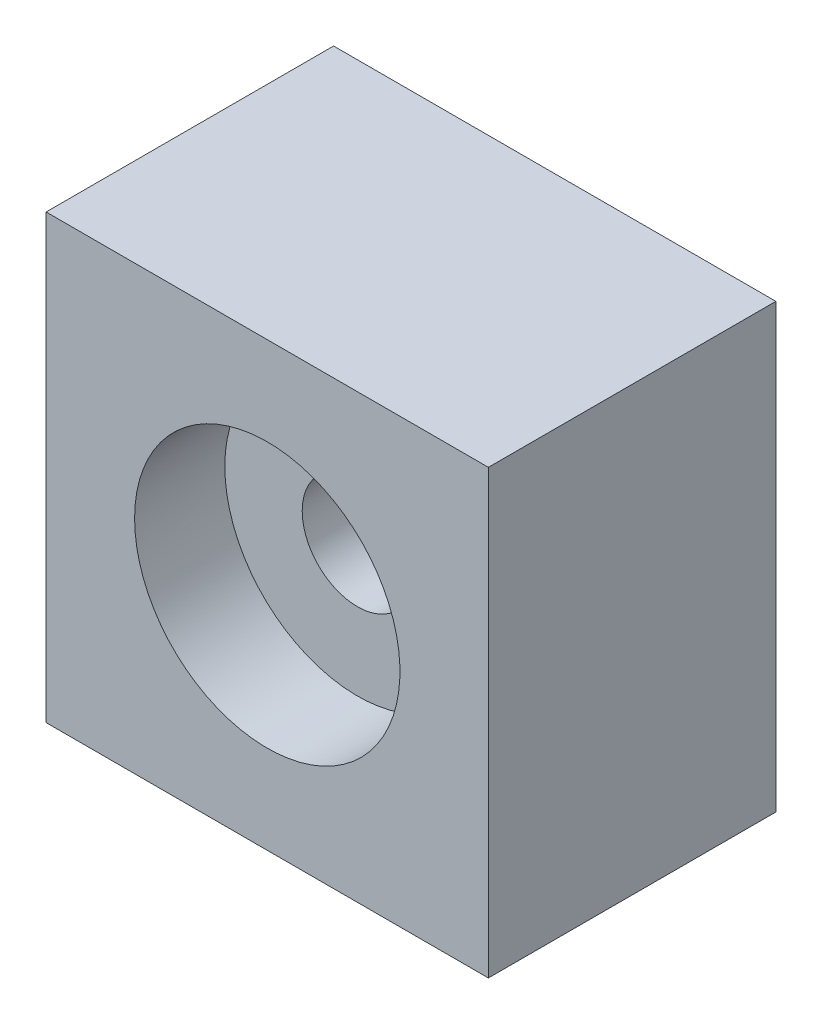
SolidWorks part; units mm, degrees
ref_plane "Front" through (0, 0, 0) normal (0, 0, 1) x (1, 0, 0)
ref_plane "Top" through (0, 0, 0) normal (0, 1, 0) x (1, 0, 0)
ref_plane "Right" through (0, 0, 0) normal (1, 0, 0) x (0, 0, -1)
sketch "Sketch1" plane through (0, 0, 0) normal (0, 0, 1) x (1, 0, 0)
  line L1 (15.875, -15.875) -> (-15.875, -15.875)
  line L2 (15.875, -15.875) -> (15.875, 15.875)
  line L3 (15.875, 15.875) -> (-15.875, 15.875)
  line L4 (-15.875, -15.875) -> (-15.875, 15.875)
  line L5 (15.875, -15.875) -> (-15.875, 15.875) construction
  line L6 (15.875, 15.875) -> (-15.875, -15.875) construction
  point P0 (0, 0)
  dimension "D1" = 31.75
extrude "Boss-Extrude1" add sketch "Sketch1" along normal blind 20.6375
sketch "Sketch2" plane through (0, 0, 0) normal (0, 0, -1) x (-1, 0, 0)
  circle A0 centre (0, 0) radius 11.1125
  dimension "D1" = 22.225
extrude "Cut-Extrude1" cut sketch "Sketch2" against normal blind 6.985
sketch "Sketch3" plane through (0, 0, 6.985) normal (0, 0, -1) x (-1, 0, 0)
  circle A0 centre (0, 0) radius 8.255
  dimension "D1" = 16.51
extrude "Cut-Extrude2" cut sketch "Sketch3" against normal blind 2.413
sketch "Sketch4" plane through (0, 0, 9.398) normal (0, 0, -1) x (-1, 0, 0)
  circle A0 centre (0, 0) radius 3.9688
  dimension "D1" = 7.9375
extrude "Cut-Extrude3" cut sketch "Sketch4" against normal through all
sketch "Sketch6" plane through (0, 0, 9.398) normal (0, 0, -1) x (-1, 0, 0)
  circle A0 centre (0, 0) radius 9.525
  dimension "D1" = 19.05
extrude "Cut-Extrude4" cut sketch "Sketch6" against normal through all from offset 4.7625 offset against normal yes
